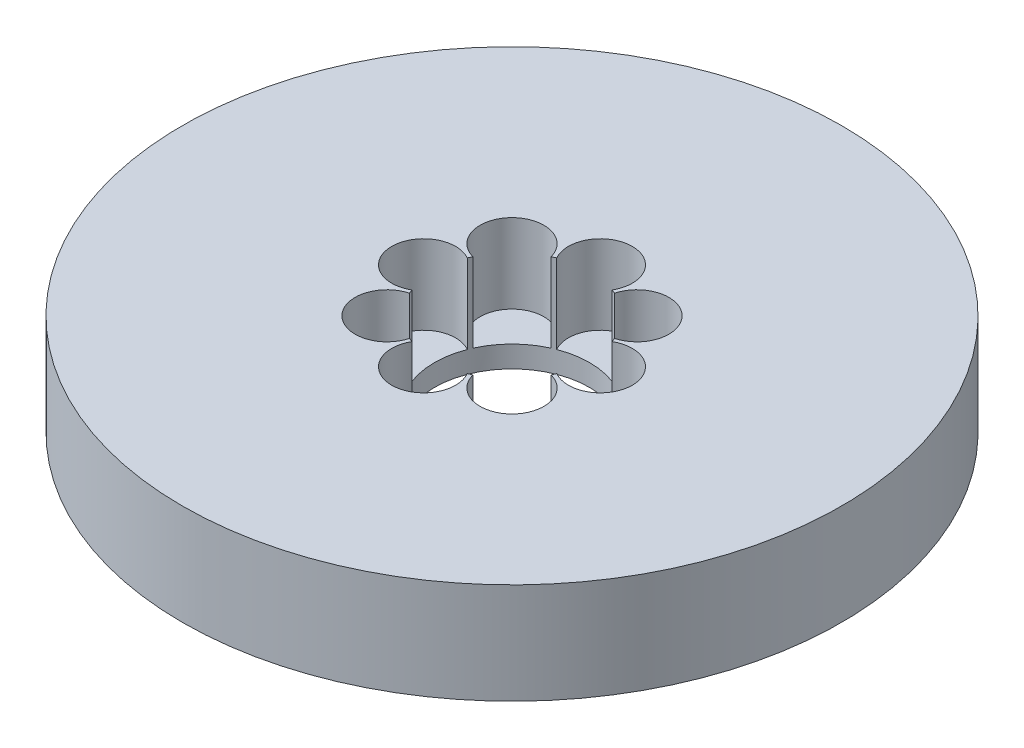
SolidWorks part; units mm, degrees
ref_plane "Front Plane" through (0, 0, 0) normal (0, 0, 1) x (1, 0, 0)
ref_plane "Top Plane" through (0, 0, 0) normal (0, 1, 0) x (1, 0, 0)
ref_plane "Right Plane" through (0, 0, 0) normal (1, 0, 0) x (0, 0, -1)
sketch "Sketch1" plane through (0, 0, 0) normal (0, 1, 0) x (1, 0, 0)
  circle A0 centre (0, 0) radius 42.5
  dimension "FLANGE_OD" = 85
extrude "Boss-Extrude1" add sketch "Sketch1" along normal blind 13
sketch "Sketch2" plane through (0, 0, 0) normal (0, 1, 0) x (1, 0, 0)
  circle A0 centre (0, 0) radius 10
  dimension "BORE_D" = 20
extrude "Cut-Extrude1" cut sketch "Sketch2" along normal through all
sketch "Sketch3" plane through (0, 13, 0) normal (0, 1, 0) x (1, 0, 0)
  circle A0 centre (0, 0) radius 11.3925 construction
  circle A1 centre (-11.3925, 0) radius 4.12
  dimension "BOLT_D" = 8.2399
  dimension "BOLT_PCD" = 22.7849
extrude "Cut-Extrude2" cut sketch "Sketch3" against normal blind 10.2193
pattern_circular "CirPattern1" count 8 over 360 about axis through (0, 0, 0) along (0, 1, 0) of "Cut-Extrude2"
